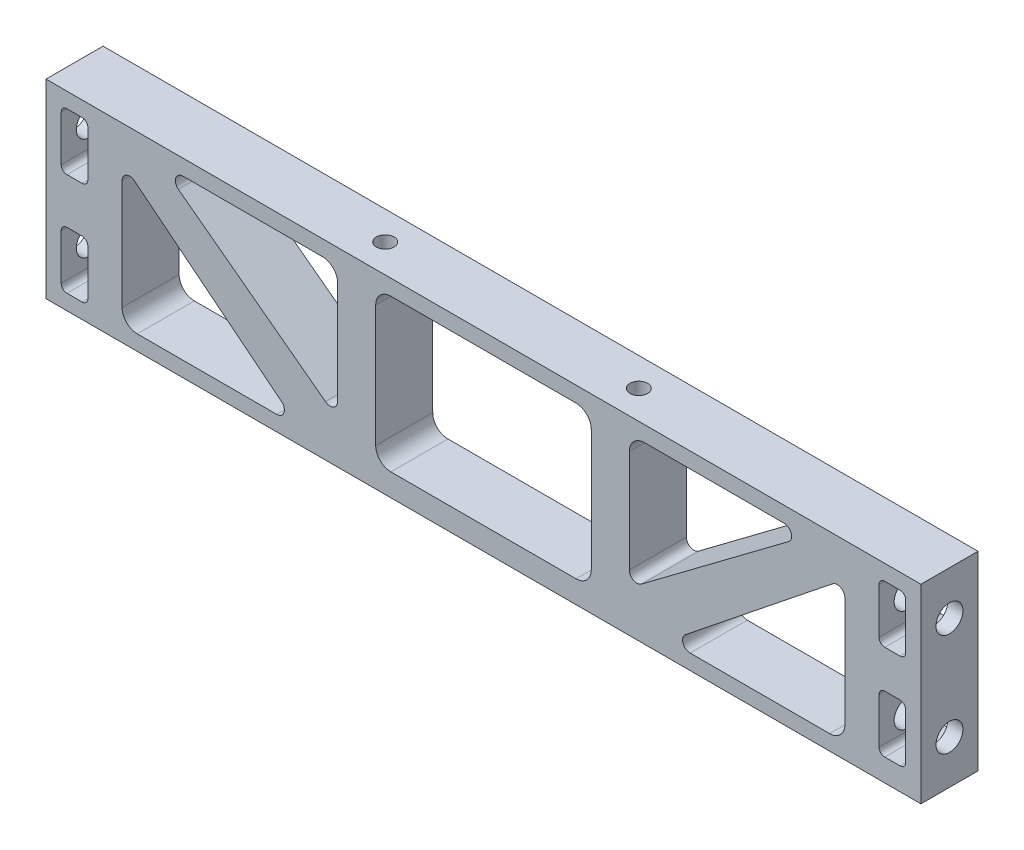
SolidWorks part; units mm, degrees
material "PE High Density"
ref_plane "Front Plane" through (0, 0, 0) normal (0, 0, 1) x (1, 0, 0)
ref_plane "Top Plane" through (0, 0, 0) normal (0, 1, 0) x (1, 0, 0)
ref_plane "Right Plane" through (0, 0, 0) normal (1, 0, 0) x (0, 0, -1)
sketch "Sketch1" plane through (0, 0, 0) normal (0, 0, 1) x (1, 0, 0)
  line L0 (-24.3417, 15.875) -> (-24.3417, -15.875) construction
  line L1 (-73.025, 15.875) -> (73.025, 15.875)
  line L2 (-73.025, 15.875) -> (-73.025, -15.875)
  line L3 (-73.025, -15.875) -> (73.025, -15.875)
  line L4 (73.025, 15.875) -> (73.025, -15.875)
  line L5 (-73.025, 15.875) -> (73.025, -15.875) construction
  line L6 (-73.025, -15.875) -> (73.025, 15.875) construction
  line L7 (24.3417, 15.875) -> (24.3417, -15.875) construction
  line L9 (-69.85, -12.7) -> (-27.5167, 12.7) construction
  line L10 (-69.85, -12.7) -> (-69.85, 12.7) construction
  line L11 (-64.3071, -11.2256) -> (-29.9209, 9.4061)
  line L12 (-73.025, -15.875) -> (-24.3417, -15.875)
  line L13 (-73.025, -15.875) -> (-73.025, 15.875)
  line L14 (-73.025, 15.875) -> (-24.3417, 15.875)
  line L15 (-24.3417, -15.875) -> (-24.3417, 15.875) construction
  line L16 (-69.85, 12.7) -> (-27.5167, 12.7) construction
  line L17 (-27.5167, -12.7) -> (-27.5167, 12.7) construction
  line L18 (-69.85, -12.7) -> (-27.5167, -12.7) construction
  line L19 (-67.4457, -9.4061) -> (-33.0595, 11.2256)
  line L20 (-69.0332, -14.0613) -> (-26.6999, 11.3387) construction
  line L21 (-69.85, -8.0448) -> (-69.85, 11.1125)
  line L22 (-70.6668, -11.3387) -> (-28.3334, 14.0613) construction
  line L23 (-68.2625, 12.7) -> (-33.4679, 12.7)
  line L24 (-63.8988, -12.7) -> (-29.1042, -12.7)
  line L25 (-27.5167, -11.1125) -> (-27.5167, 8.0448)
  line L26 (-15.6238, -11.2256) -> (18.7624, 9.4061)
  line L27 (-18.7624, -9.4061) -> (15.6238, 11.2256)
  line L28 (-21.1667, -8.0448) -> (-21.1667, 11.1125)
  line L29 (-19.5792, 12.7) -> (15.2154, 12.7)
  line L30 (-15.2154, -12.7) -> (19.5792, -12.7)
  line L31 (21.1667, -11.1125) -> (21.1667, 8.0448)
  line L32 (-21.1667, -12.7) -> (21.1667, 12.7) construction
  line L33 (-21.1667, -12.7) -> (-21.1667, 12.7) construction
  line L34 (-21.1667, 12.7) -> (21.1667, 12.7) construction
  line L35 (21.1667, -12.7) -> (21.1667, 12.7) construction
  line L36 (-21.1667, -12.7) -> (21.1667, -12.7) construction
  line L37 (33.0595, -11.2256) -> (67.4457, 9.4061)
  line L38 (29.9209, -9.4061) -> (64.3071, 11.2256)
  line L39 (27.5167, -8.0448) -> (27.5167, 11.1125)
  line L40 (29.1042, 12.7) -> (63.8988, 12.7)
  line L41 (33.4679, -12.7) -> (68.2625, -12.7)
  line L42 (69.85, -11.1125) -> (69.85, 8.0448)
  line L43 (27.5167, -12.7) -> (69.85, 12.7) construction
  line L44 (27.5167, -12.7) -> (27.5167, 12.7) construction
  line L45 (27.5167, 12.7) -> (69.85, 12.7) construction
  line L46 (69.85, -12.7) -> (69.85, 12.7) construction
  line L47 (27.5167, -12.7) -> (69.85, -12.7) construction
  line L59 (-64.3071, -11.2256) -> (-15.6238, -11.2256) construction
  line L60 (-69.85, 15.875) -> (-69.85, -15.875)
  arc A0 (-33.4679, 12.7) -> (-33.0595, 11.2256) centre (-33.4679, 11.9062) cw
  arc A1 (-69.85, -8.0448) -> (-67.4457, -9.4061) centre (-68.2625, -8.0448) ccw
  arc A2 (-69.85, 11.1125) -> (-68.2625, 12.7) centre (-68.2625, 11.1125) cw
  arc A3 (-27.5167, 8.0448) -> (-29.9209, 9.4061) centre (-29.1042, 8.0448) ccw
  arc A4 (-63.8988, -12.7) -> (-64.3071, -11.2256) centre (-63.8988, -11.9062) cw
  arc A5 (-27.5167, -11.1125) -> (-29.1042, -12.7) centre (-29.1042, -11.1125) cw
  arc A6 (15.2154, 12.7) -> (15.6238, 11.2256) centre (15.2154, 11.9062) cw
  arc A7 (-21.1667, -8.0448) -> (-18.7624, -9.4061) centre (-19.5792, -8.0448) ccw
  arc A8 (-21.1667, 11.1125) -> (-19.5792, 12.7) centre (-19.5792, 11.1125) cw
  arc A9 (21.1667, 8.0448) -> (18.7624, 9.4061) centre (19.5792, 8.0448) ccw
  arc A10 (-15.2154, -12.7) -> (-15.6238, -11.2256) centre (-15.2154, -11.9062) cw
  arc A11 (21.1667, -11.1125) -> (19.5792, -12.7) centre (19.5792, -11.1125) cw
  arc A12 (63.8988, 12.7) -> (64.3071, 11.2256) centre (63.8988, 11.9062) cw
  arc A13 (27.5167, -8.0448) -> (29.9209, -9.4061) centre (29.1042, -8.0448) ccw
  arc A14 (27.5167, 11.1125) -> (29.1042, 12.7) centre (29.1042, 11.1125) cw
  arc A15 (69.85, 8.0448) -> (67.4457, 9.4061) centre (68.2625, 8.0448) ccw
  arc A16 (33.4679, -12.7) -> (33.0595, -11.2256) centre (33.4679, -11.9062) cw
  arc A17 (69.85, -11.1125) -> (68.2625, -12.7) centre (68.2625, -11.1125) cw
  point P0 (0, 0)
  point P26 (-30.6022, 12.7)
  point P29 (-69.85, -10.8487)
  point P35 (-27.5167, 10.8487)
  point P38 (-66.7645, -12.7)
  dimension "D7" = 0.7937
  dimension "D8" = 1.5875
  dimension "D9" = 1.5875
  dimension "D10" = 1.5875
  dimension "D11" = 0.7937
  dimension "D12" = 1.5875
  dimension "D1" = 31.75
  dimension "CrossBraceLength" = 146.05
  dimension "D4" = 48.6833
  dimension "D14" = 48.6833
  dimension "D6" = 3.175
  dimension "D2" = 1.5875
  dimension "D5" = 1.5875
  dimension "D3" = 3
  dimension "D13" = 3
extrude "Boss-Extrude1" [suppressed] add sketch "Sketch1" along normal blind 9.525
sketch "Sketch2" plane through (0, 0, 0) normal (0, 0, 1) x (1, 0, 0)
  line L0 (-63.5, 15.3) -> (-63.5, -16.45) construction
  line L1 (-73.025, 15.3) -> (73.025, 15.3)
  line L2 (-73.025, 15.3) -> (-73.025, -16.45)
  line L3 (-73.025, -16.45) -> (73.025, -16.45)
  line L4 (73.025, 15.3) -> (73.025, -16.45)
  line L5 (-73.025, 15.3) -> (73.025, -16.45) construction
  line L6 (-73.025, -16.45) -> (73.025, 15.3) construction
  line L7 (0, 15.3) -> (0, -16.45) construction
  line L8 (-63.5, -16.45) -> (-63.5, 15.3) construction
  line L9 (63.5, 15.3) -> (63.5, -16.45) construction
  line L10 (-21.1667, 15.3) -> (-21.1667, -16.45) construction
  line L11 (-73.025, -0.575) -> (73.025, -0.575) construction
  line L12 (21.1667, 15.3) -> (21.1667, -16.45) construction
  line L14 (-63.5, -16.45) -> (-63.5, 15.3) construction
  line L15 (-63.5, 15.3) -> (-21.1667, 15.3)
  line L19 (-63.5, 15.3) -> (-21.1667, -16.45) construction
  line L20 (-63.5, -16.45) -> (-21.1667, -16.45)
  line L21 (-21.1667, 15.3) -> (-63.5, 15.3)
  line L22 (-63.5, -16.45) -> (-21.1667, -16.45)
  line L23 (-63.5, -16.45) -> (-63.5, 15.3) construction
  line L27 (-63.5, 15.3) -> (-21.1667, -16.45) construction
  line L28 (-50.927, 10.414) -> (-26.3737, -8.001)
  line L29 (-60.325, -11.3725) -> (-60.325, 6.985)
  line L48 (-57.785, -13.9125) -> (-34.5017, -13.9125)
  line L61 (-69.5325, 12.7625) -> (-66.9925, 12.7625)
  line L62 (-70.485, 11.81) -> (-70.485, 4.19)
  line L63 (-69.5325, 3.2375) -> (-66.9925, 3.2375)
  line L64 (-66.04, 11.81) -> (-66.04, 4.19)
  line L65 (-70.485, 12.7625) -> (-66.04, 3.2375) construction
  line L66 (-70.485, 3.2375) -> (-66.04, 12.7625) construction
  line L67 (-68.2625, 15.3) -> (-68.2625, -16.45) construction
  line L68 (-68.2625, 3.2375) -> (-68.2625, 11.967) construction
  line L69 (-70.485, 8) -> (-66.04, 8) construction
  line L70 (-70.485, -9.15) -> (-66.04, -9.15) construction
  line L71 (-68.2625, -4.3875) -> (-68.2625, -13.117) construction
  line L72 (-70.485, -4.3875) -> (-66.04, -13.9125) construction
  line L73 (-70.485, -13.9125) -> (-66.04, -4.3875) construction
  line L74 (-66.04, -12.96) -> (-66.04, -5.34)
  line L75 (-69.5325, -4.3875) -> (-66.9925, -4.3875)
  line L76 (-70.485, -12.96) -> (-70.485, -5.34)
  line L77 (-69.5325, -13.9125) -> (-66.9925, -13.9125)
  line L78 (-58.262, 7.977) -> (-33.7087, -11.6505)
  line L79 (70.485, -12.7) -> (66.04, -3.175) construction
  line L80 (70.485, -3.175) -> (66.04, -12.7) construction
  line L81 (68.2625, -3.175) -> (68.2625, -11.967) construction
  line L82 (70.485, -7.9375) -> (66.04, -7.9375) construction
  line L83 (70.485, 7.9375) -> (66.04, 7.9375) construction
  line L84 (68.2625, 3.175) -> (68.2625, 11.967) construction
  line L85 (68.2625, 15.875) -> (68.2625, -15.875) construction
  line L86 (70.485, 3.175) -> (66.04, 12.7) construction
  line L87 (70.485, 12.7) -> (66.04, 3.175) construction
  line L88 (69.5325, -12.7) -> (66.9925, -12.7)
  line L89 (70.485, -11.7475) -> (70.485, -4.1275)
  line L90 (69.5325, -3.175) -> (66.9925, -3.175)
  line L91 (66.04, -11.7475) -> (66.04, -4.1275)
  line L92 (66.04, 11.7475) -> (66.04, 4.1275)
  line L93 (69.5325, 3.175) -> (66.9925, 3.175)
  line L94 (70.485, 11.7475) -> (70.485, 4.1275)
  line L95 (69.5325, 12.7) -> (66.9925, 12.7)
  line L96 (73.025, 15.3) -> (73.025, -16.45)
  line L97 (-63.5, 15.3) -> (-24.3417, 15.3)
  line L99 (-60.325, -16.45) -> (-60.325, 15.3) construction
  line L102 (-24.3417, 10.16) -> (-24.3417, -6.985)
  line L104 (-50.165, 12.7) -> (-26.8817, 12.7)
  line L105 (24.3417, 10.16) -> (24.3417, -6.985)
  line L106 (-24.3417, 15.3) -> (-24.3417, -16.45) construction
  line L107 (50.165, 12.7) -> (26.8817, 12.7)
  line L108 (50.927, 10.414) -> (26.3737, -8.001)
  line L109 (57.785, -13.9125) -> (34.5017, -13.9125)
  line L110 (58.262, 7.977) -> (33.7087, -11.6505)
  line L111 (60.325, -11.3725) -> (60.325, 6.985)
  line L112 (0, -16.45) -> (0, -13.275)
  line L114 (-15.4517, 12.7) -> (15.4517, 12.7)
  line L115 (-17.9917, 10.16) -> (-17.9917, -10.16)
  line L116 (-15.4517, -12.7) -> (15.4517, -12.7)
  line L117 (17.9917, 10.16) -> (17.9917, -10.16)
  line L118 (-17.9917, 12.7) -> (17.9917, -12.7) construction
  line L119 (-17.9917, -12.7) -> (17.9917, 12.7) construction
  arc A36 (-66.9925, 3.2375) -> (-66.04, 4.19) centre (-66.9925, 4.19) ccw
  arc A37 (-66.9925, 12.7625) -> (-66.04, 11.81) centre (-66.9925, 11.81) cw
  arc A38 (-69.5325, 3.2375) -> (-70.485, 4.19) centre (-69.5325, 4.19) cw
  arc A39 (-69.5325, 12.7625) -> (-70.485, 11.81) centre (-69.5325, 11.81) ccw
  arc A40 (-69.5325, -13.9125) -> (-70.485, -12.96) centre (-69.5325, -12.96) cw
  arc A41 (-69.5325, -4.3875) -> (-70.485, -5.34) centre (-69.5325, -5.34) ccw
  arc A42 (-66.9925, -13.9125) -> (-66.04, -12.96) centre (-66.9925, -12.96) ccw
  arc A43 (-66.9925, -4.3875) -> (-66.04, -5.34) centre (-66.9925, -5.34) cw
  arc A44 (66.9925, -3.175) -> (66.04, -4.1275) centre (66.9925, -4.1275) ccw
  arc A45 (66.9925, -12.7) -> (66.04, -11.7475) centre (66.9925, -11.7475) cw
  arc A46 (69.5325, -3.175) -> (70.485, -4.1275) centre (69.5325, -4.1275) cw
  arc A47 (69.5325, -12.7) -> (70.485, -11.7475) centre (69.5325, -11.7475) ccw
  arc A48 (69.5325, 12.7) -> (70.485, 11.7475) centre (69.5325, 11.7475) cw
  arc A49 (69.5325, 3.175) -> (70.485, 4.1275) centre (69.5325, 4.1275) ccw
  arc A50 (66.9925, 12.7) -> (66.04, 11.7475) centre (66.9925, 11.7475) ccw
  arc A51 (66.9925, 3.175) -> (66.04, 4.1275) centre (66.9925, 4.1275) cw
  arc A52 (-57.785, -13.9125) -> (-60.325, -11.3725) centre (-57.785, -11.3725) cw
  arc A53 (-60.325, 6.985) -> (-58.262, 7.977) centre (-59.055, 6.985) cw
  arc A54 (-34.5017, -13.9125) -> (-33.7087, -11.6505) centre (-34.5017, -12.6425) ccw
  arc A55 (-26.8817, 12.7) -> (-24.3417, 10.16) centre (-26.8817, 10.16) cw
  arc A56 (-26.3737, -8.001) -> (-24.3417, -6.985) centre (-25.6117, -6.985) ccw
  arc A57 (-50.927, 10.414) -> (-50.165, 12.7) centre (-50.165, 11.43) cw
  arc A58 (26.3737, -8.001) -> (24.3417, -6.985) centre (25.6117, -6.985) cw
  arc A59 (26.8817, 12.7) -> (24.3417, 10.16) centre (26.8817, 10.16) ccw
  arc A60 (50.927, 10.414) -> (50.165, 12.7) centre (50.165, 11.43) ccw
  arc A61 (57.785, -13.9125) -> (60.325, -11.3725) centre (57.785, -11.3725) ccw
  arc A62 (34.5017, -13.9125) -> (33.7087, -11.6505) centre (34.5017, -12.6425) cw
  arc A63 (60.325, 6.985) -> (58.262, 7.977) centre (59.055, 6.985) ccw
  arc A64 (-15.4517, -12.7) -> (-17.9917, -10.16) centre (-15.4517, -10.16) cw
  arc A65 (-17.9917, 10.16) -> (-15.4517, 12.7) centre (-15.4517, 10.16) cw
  arc A66 (17.9917, 10.16) -> (15.4517, 12.7) centre (15.4517, 10.16) ccw
  arc A67 (17.9917, -10.16) -> (15.4517, -12.7) centre (15.4517, -10.16) cw
  point P16 (-68.2625, 8)
  point P18 (-65.405, 13.335)
  point P19 (-23.0717, -18.415)
  point P24 (-63.5, 12.7)
  point P26 (-24.3417, 12.7)
  point P34 (-61.595, 18.415)
  point P36 (-19.2617, -13.335)
  point P65 (0, 0)
  point P124 (-68.2625, -9.15)
  point P168 (68.2625, -7.9375)
  point P169 (68.2625, 7.9375)
  dimension "D19" = 0.9525
  dimension "D20" = 0.9525
  dimension "D21" = 0.9525
  dimension "D22" = 0.9525
  dimension "D6" = 2.54
  dimension "D8" = 1.27
  dimension "D9" = 1.27
  dimension "D11" = 2.54
  dimension "D12" = 1.27
  dimension "D13" = 1.27
  dimension "D16" = 2.54
  dimension "D1" = 146.05
  dimension "D2" = 31.75
  dimension "D3" = 9.525
  dimension "D17" = 4.445
  dimension "D18" = 9.525
  dimension "D23" = 4.7625
  dimension "D4" = 42.3333
  dimension "D5" = 42.3333
  dimension "D14" = 3.175
  dimension "D15" = 35.9833
  dimension "D24" = 7.3
  dimension "D7" = 3.175
  dimension "D10" = 3.175
extrude "Boss-Extrude2" add sketch "Sketch2" along normal blind 9.525 contours L4 L1 L2 L3 region at (-68.2625, 13.8054, 0)
sketch "Sketch3" plane through (-73.025, 0, 0) normal (-1, 0, 0) x (0, 0, 1)
  line L0 (9.525, 15.3) -> (0, 15.3) construction
  line L1 (0, -0.575) -> (9.525, -0.575) construction
  line L3 (4.7625, -16.45) -> (4.7625, 15.3) construction
  line L4 (9.525, -16.45) -> (0, -16.45) construction
  line L5 (0, 15.3) -> (0, -16.45) construction
  line L6 (9.525, 15.3) -> (9.525, -16.45) construction
  circle A0 centre (4.7625, 8) radius 2.2479
  circle A1 centre (4.7625, -9.15) radius 2.2479
  dimension "D2" = 4.4958
  dimension "D1" = 7.3
extrude "Cut-Extrude1" cut sketch "Sketch3" against normal blind 11.1125
sketch "Sketch4" plane through (0, 15.3, 0) normal (0, 1, 0) x (1, 0, 0)
  line L2 (17.9917, -9.525) -> (17.9917, 0) construction
  line L3 (17.9917, -9.525) -> (17.9917, 0) construction
  line L4 (73.025, 0) -> (-73.025, 0)
  line L5 (-73.025, 0) -> (-73.025, -9.525)
  line L6 (-73.025, -9.525) -> (73.025, -9.525)
  line L7 (73.025, -9.525) -> (73.025, 0)
  line L8 (73.025, 0) -> (-73.025, 0) construction
  line L9 (-73.025, 0) -> (-73.025, -9.525) construction
  line L10 (-73.025, -9.525) -> (73.025, -9.525) construction
  line L11 (73.025, -9.525) -> (73.025, 0) construction
  line L12 (-17.9917, -9.525) -> (-17.9917, 0) construction
  line L13 (-17.9917, -9.525) -> (-17.9917, 0) construction
  line L14 (-24.3417, -9.525) -> (-24.3417, 0) construction
  line L15 (-24.3417, -9.525) -> (-24.3417, 0) construction
  line L16 (24.3417, -9.525) -> (24.3417, 0) construction
  line L17 (24.3417, -9.525) -> (24.3417, 0) construction
  line L18 (24.3417, -9.525) -> (17.9917, 0) construction
  line L19 (17.9917, -9.525) -> (24.3417, 0) construction
  circle A0 centre (21.1667, -4.7625) radius 1.4732
  dimension "D2" = 2.9464
  dimension "D1" = 0
extrude "Cut-Extrude2" cut sketch "Sketch4" against normal blind 12.7 contours A0
ref_plane "Plane1" through (0, -0.575, 0) normal (0, 1, 0) x (1, 0, 0)
mirror "Mirror2" about plane through (0, -0.575, 0) normal (0, 1, 0) of "Cut-Extrude2" second plane through (0, 0, 0) second plane normal (1, 0, 0)
mirror "Mirror3" about plane through (0, 0, 0) normal (1, 0, 0) of "Cut-Extrude1"
equation "\"Plate Width\" = 3.5in"
equation "\"Plate Thickness\" = 0.375in"
equation "\"Num holes\" = 4"
equation "\"Plate Height\" = 1.25in"
equation "\"Top Plate Width\" = 4.5in"
equation "\"Plate Clearance Hole Diameter\" = 0.125in"
equation "\"Plate Tap Hole Diameter\" = 0.116in"
equation "\"Bottom Plate Length\" = 6.5in"
equation "\"CrossBraceLength@Sketch1\" = \"Bottom Plate Length\" - 2 * \"Plate Thickness\""
equation "\"D1@Sketch1\"=\"Plate Height\""
equation "\"num_triangle_holes\"= 3"
equation "\"D3@Sketch1\"=\"num_triangle_holes\""
equation "\"D4@Sketch1\"=( \"Bottom Plate Length\" - 2 * \"Plate Thickness\" ) / \"num_triangle_holes\""
equation "\"BorderThickness\"= 0.125"
equation "\"D6@Sketch1\"=\"BorderThickness\""
equation "\"D2@Sketch1\"=\"BorderThickness\"/2"
equation "\"D9@Sketch1\"=\"BorderThickness\"/2"
equation "\"D8@Sketch1\"=\"BorderThickness\"/2"
equation "\"D7@Sketch1\"=\"BorderThickness\"/4"
equation "\"D10@Sketch1\"=\"BorderThickness\"/2"
equation "\"D11@Sketch1\"=\"BorderThickness\"/4"
equation "\"D12@Sketch1\"=\"BorderThickness\"/2"
equation "\"D13@Sketch1\"=\"num_triangle_holes\""
equation "\"D14@Sketch1\"=( \"Bottom Plate Length\" - 2 * \"Plate Thickness\" ) / \"num_triangle_holes\""
equation "\"D1@Boss-Extrude1\"=\"Plate Thickness\""
equation "\"D1@Sketch2\"=\"Bottom Plate Length\" - 2 * \"Plate Thickness\""
equation "\"D2@Sketch2\"=\"Plate Height\""
equation "\"wall_thickness\"= 0.375"
equation "\"D3@Sketch2\"=\"wall_thickness\""
equation "\"D1@Boss-Extrude2\"=\"Plate Thickness\""
equation "\"D23@Sketch2\"=\"wall_thickness\"/2"
equation "\"Number Eight Clearance Size\" = 0.177in"
equation "\"D2@Sketch3\"=\"Number Eight Clearance Size\""
equation "\"D1@Cut-Extrude1\"=(0.75 - \"Plate Thickness\") + 0.0625"
equation "\"D4@Sketch2\"=( ( \"Bottom Plate Length\" - 2 * \"Plate Thickness\" ) - \"Plate Thickness\" * 2 ) /3"
equation "\"D5@Sketch2\"=( ( \"Bottom Plate Length\" - 2 * \"Plate Thickness\" ) - \"Plate Thickness\" * 2 ) /3"
equation "\"D14@Sketch2\"=\"BorderThickness\""
equation "\"D15@Sketch2\"=( ( ( \"Bottom Plate Length\" - 2 * \"Plate Thickness\" ) - \"Plate Thickness\" * 2 ) /3 ) - \"BorderThickness\"*2"
equation "\"D24@Sketch2\"=7.3mm"
